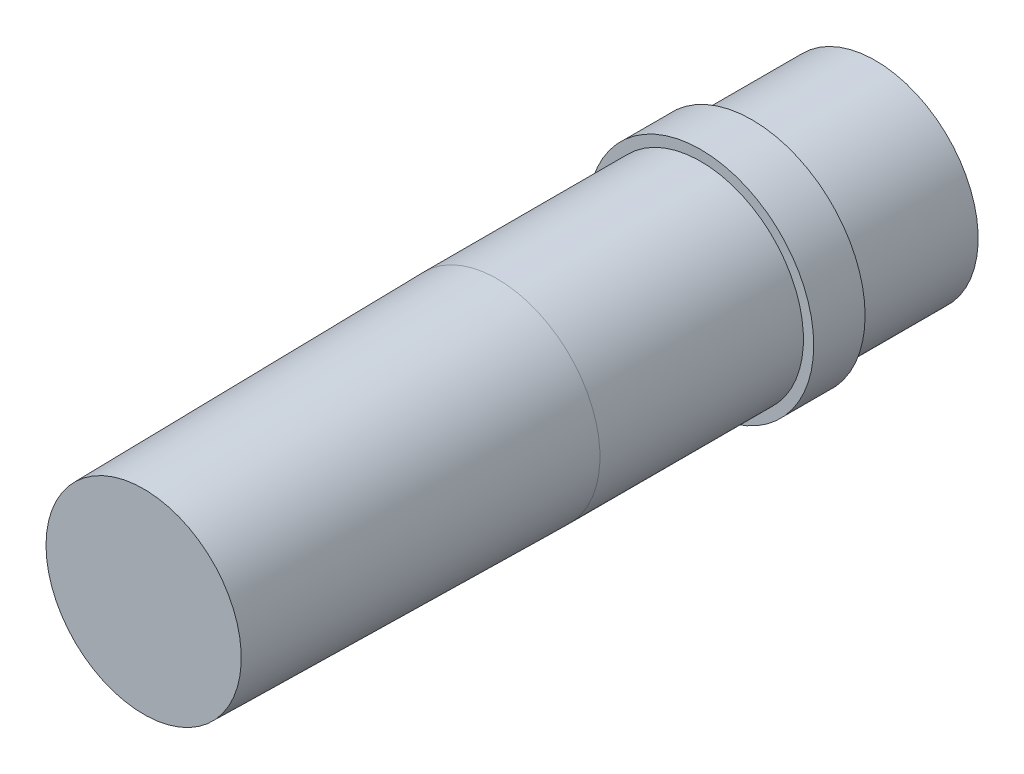
SolidWorks part; units mm, degrees
ref_plane "Front" through (0, 0, 0) normal (0, 0, 1) x (1, 0, 0)
ref_plane "Top" through (0, 0, 0) normal (0, 1, 0) x (1, 0, 0)
ref_plane "Right" through (0, 0, 0) normal (1, 0, 0) x (0, 0, -1)
sketch "Sketch1" plane through (0, 0, 0) normal (0, 1, 0) x (1, 0, 0)
  line L0 (0, 1.5998) -> (0, -1.3793) construction
  line L1 (0, 3.56) -> (-0.5, 3.56)
  line L2 (-0.5, 3.56) -> (-0.5, 2.96)
  line L3 (-0.5, 2.96) -> (-0.55, 2.96)
  line L4 (-0.55, 2.96) -> (-0.55, 2.71)
  line L5 (-0.55, 2.71) -> (-0.5, 2.71)
  line L6 (-0.5, 2.71) -> (-0.5, 1.72)
  line L7 (-0.475, 0) -> (0, 0)
  line L8 (-0.5, 1.72) -> (-0.475, 0)
  line L9 (0, 3.56) -> (0, 0)
  dimension "D1" = 0.5
  dimension "D2" = 3.56
  dimension "D3" = 0.475
  dimension "D4" = 1.84
  dimension "D5" = 0.55
  dimension "D6" = 0.25
  dimension "D7" = 0.6
revolve "Revolve1" add sketch "Sketch1" angle 360 about L0
sketch "Sketch2" plane through (0, 0, -3.56) normal (0, 0, -1) x (-1, 0, 0)
  circle A0 centre (0, 0) radius 0.425
  dimension "D1" = 0.85
extrude "Cut-Extrude1" cut sketch "Sketch2" against normal blind 1.5
